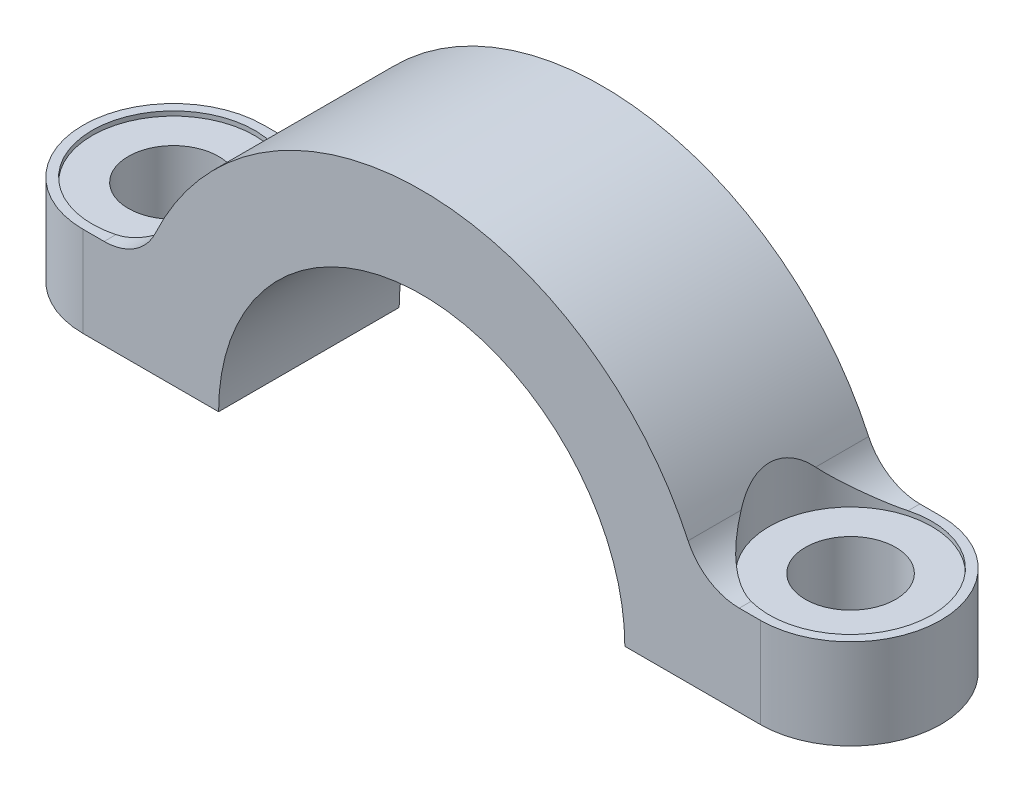
SolidWorks part; units mm, degrees
ref_plane "Front Plane" through (0, 0, 0) normal (0, 0, 1) x (1, 0, 0)
ref_plane "Top Plane" through (0, 0, 0) normal (0, 1, 0) x (1, 0, 0)
ref_plane "Right Plane" through (0, 0, 0) normal (1, 0, 0) x (0, 0, -1)
sketch "Sketch1" plane through (0, 0, 0) normal (0, 0, 1) x (1, 0, 0)
  line L0 (-19, 0) -> (-9, 0)
  line L1 (9, 0) -> (19, 0)
  line L2 (0, -9) -> (0, 9) construction
  line L3 (-9, 0) -> (9, 0) construction
  line L4 (14.0712, 4) -> (19, 4)
  line L5 (-19, 4) -> (-14.0712, 4)
  line L6 (-19, 4) -> (-19, 0)
  line L7 (19, 4) -> (19, 0)
  line L8 (12.3693, 4) -> (19, 4) construction
  line L9 (-19, 4) -> (-12.3693, 4) construction
  arc A0 (9, 0) -> (-9, 0) centre (0, 0) ccw
  arc A1 (11.8017, 5.4516) -> (-11.8017, 5.4516) centre (0, 0) ccw
  arc A2 (12.3693, 4) -> (-12.3693, 4) centre (0, 0) ccw construction
  arc A3 (14.0712, 4) -> (11.8017, 5.4516) centre (14.0712, 6.5) cw
  arc A4 (-11.8017, 5.4516) -> (-14.0712, 4) centre (-14.0712, 6.5) cw
  point P4 (0, 0)
  point P11 (0, 0)
  point P13 (0, 0)
  dimension "D1" = 9
  dimension "D5" = 2.5
  dimension "D2" = 19
  dimension "D3" = 19
  dimension "D4" = 4
extrude "Boss-Extrude1" add sketch "Sketch1" along normal mid plane 8
sketch "Sketch2" plane through (0, 0, 0) normal (0, 1, 0) x (1, 0, 0)
  line L0 (0, -4) -> (0, 4) construction
  line L1 (11.8017, 4) -> (-11.8017, 4) construction
  line L2 (-15, 0) -> (15, 0) construction
  circle A0 centre (-15, 0) radius 2
  circle A1 centre (15, 0) radius 2
  point P6 (0, 0)
  point P10 (0, 0)
  dimension "D2" = 4
  dimension "D3" = 4
  dimension "D1" = 30
extrude "Cut-Extrude2" cut sketch "Sketch2" along normal blind 8
fillet "Fillet2" 2 edges at (19, 2, 4) (19, 2, -4) type full round first side face at (0, 4.2788, 4) second side face at (0, 4.2788, -4) middle face at (19, 2, 0)
fillet "Fillet3" 2 edges at (-19, 2, 4) (-19, 2, -4) type full round first side face at (-0.8, 4.2788, 4) second side face at (-0.8, 4.2788, -4) middle face at (-19, 2, 0)
sketch "Sketch3" plane through (0, 0, 0) normal (0, 1, 0) x (1, 0, 0)
  circle A0 centre (-15, 0) radius 3.6
  circle A1 centre (15, 0) radius 3.6
  dimension "D1" = 7.2
  dimension "D2" = 7.2
extrude "Cut-Extrude3" cut sketch "Sketch3" along normal blind 8 from offset 3.8
